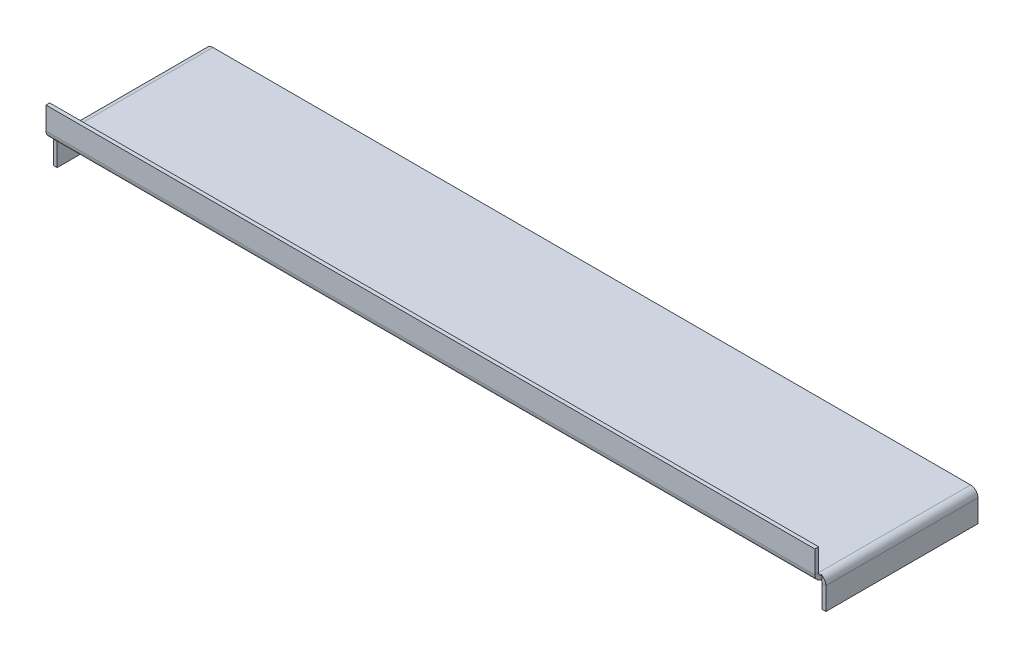
SolidWorks part; units mm, degrees
note: The reader was unsure of these and kept them because the rebuilt part matched: flange length of "Edge-Flange1", "Edge-Flange2", "Edge-Flange3".
ref_plane "Front Plane" through (0, 0, 0) normal (0, 0, 1) x (1, 0, 0)
ref_plane "Top Plane" through (0, 0, 0) normal (0, 1, 0) x (1, 0, 0)
ref_plane "Right Plane" through (0, 0, 0) normal (1, 0, 0) x (0, 0, -1)
sketch "Sketch1" plane through (0, 0, 0) normal (0, 1, 0) x (1, 0, 0)
  line L1 (244.844, -50.8) -> (-244.844, -50.8)
  line L2 (244.844, -50.8) -> (244.844, 50.8)
  line L3 (244.844, 50.8) -> (-244.844, 50.8)
  line L4 (-244.844, -50.8) -> (-244.844, 50.8)
  line L5 (244.844, -50.8) -> (-244.844, 50.8) construction
  line L6 (244.844, 50.8) -> (-244.844, -50.8) construction
  point P0 (0, 0)
  dimension "D1" = 489.688
  dimension "D2" = 101.6
base flange "Base-Flange1" sketch "Sketch1" thickness 2.3622 reverse thickness direction no parameters "D1"=10
edge flange "Edge-Flange1" sketch "Sketch8" flange angle 90 flange length 19.05 flange position material inside bend radius 2.36 thickness 2.3622 relief rectangular parameters "D6"=10
sketch "Sketch8" plane through (0, 0, 50.8) normal (0, 0, 1) x (1, 0, 0)
  line L2 (-244.844, 0) -> (-244.844, 16.6878)
  line L3 (-244.844, 16.6878) -> (244.844, 16.6878)
  line L4 (244.844, 16.6878) -> (244.844, 0)
  line L11 (-244.844, 0) -> (244.844, 0) construction
  line L12 (-244.844, 0) -> (244.844, 0)
bend "EdgeBend1" bend radius 2.36 bend angle 90 parameters "D5"=1
edge flange "Edge-Flange2" sketch "Sketch11" flange angle 90 flange length 19.05 flange position material inside bend radius 2.36 thickness 2.3622 relief none parameters "D6"=10
sketch "Sketch11" plane through (-244.844, -2.3622, 0) normal (-1, 0, 0) x (0, 0, -1)
  line L0 (50.8, 0) -> (-46.0778, 0) construction
  line L1 (50.8, 0) -> (-46.0778, 0)
  line L2 (-46.0778, 0) -> (-46.0778, 16.6878)
  line L3 (-46.0778, 16.6878) -> (50.8, 16.6878)
  line L4 (50.8, 16.6878) -> (50.8, 0)
bend "EdgeBend2" bend radius 2.36 bend angle 90 parameters "D5"=2
edge flange "Edge-Flange3" sketch "Sketch14" flange angle 90 flange length 19.05 flange position material outside bend radius 2.36 thickness 2.3622 relief none parameters "D6"=10
sketch "Sketch14" plane through (244.844, -2.3622, 0) normal (1, 0, 0) x (0, 0, 1)
  line L2 (-50.8, 0) -> (-50.8, 16.6878)
  line L3 (-50.8, 16.6878) -> (46.0778, 16.6878)
  line L4 (46.0778, 16.6878) -> (46.0778, 0)
  line L7 (46.0778, 0) -> (-50.8, 0) construction
  line L8 (46.0778, 0) -> (-50.8, 0)
bend "EdgeBend3" bend radius 2.36 bend angle 90 parameters "D5"=3
sketch "Bend-Lines1" [suppressed] plane through (0, 0, 0) normal (0, 1, 0) x (1, 0, 0)
sketch "Bounding-Box1" [suppressed] plane through (0, 0, 0) normal (0, 1, 0) x (1, 0, 0)
sheet metal parameters "Sheet-Metal1" thickness 2.3622 parameters "D1"=10
flat pattern "Flat-Pattern1" [suppressed]
sketch "Bend-Lines2" plane through (0, 0, 0) normal (0, 1, 0) x (1, 0, 0)
sketch3d "Bounding-Box2" [suppressed]
  line L0 (-255.27, -88.9, 0) -> (255.27, -88.9, 0) construction
  line L1 (-255.27, 88.9, 0) -> (255.27, 88.9, 0) construction
  line L2 (-255.27, -88.9, 0) -> (-255.27, 88.9, 0) construction
  line L3 (255.27, -88.9, 0) -> (255.27, 88.9, 0) construction
sheet metal parameters "Sheet-Metal2" thickness 2.3622 parameters "D1"=10
flat pattern "Flat-Pattern1"
sketch "Bend-Lines2" plane through (0, 0, 0) normal (0, 1, 0) x (1, 0, 0)
  line L0 (-255.27, -86.959) -> (255.27, -86.959) construction
  line L1 (-255.27, -86.959) -> (255.27, -86.959) construction
sketch3d "Bounding-Box2" [suppressed]
  line L0 (255.27, -104.0679, 0) -> (-255.27, -104.0679, 0) construction
  line L1 (255.27, 88.9, 0) -> (-255.27, 88.9, 0) construction
  line L2 (255.27, -104.0679, 0) -> (255.27, 88.9, 0) construction
  line L3 (-255.27, -104.0679, 0) -> (-255.27, 88.9, 0) construction
bend of the flat pattern "Flatten-<EdgeBend1>1"
sheet metal parameters "Sheet-Metal3" thickness 2.3622 parameters "D1"=10
flat pattern "Flat-Pattern1"
sketch "Bend-Lines2" plane through (0, 0, 0) normal (0, 1, 0) x (1, 0, 0)
  line L0 (-255.27, -86.959) -> (255.27, -86.959) construction
  line L1 (-255.27, -86.959) -> (255.27, -86.959) construction
  line L2 (-253.329, 88.9) -> (-253.329, -84.1778) construction
  line L3 (-253.329, 88.9) -> (-253.329, -84.1778) construction
sketch3d "Bounding-Box2" [suppressed]
  line L0 (255.27, -104.0679, 0) -> (-270.4379, -104.0679, 0) construction
  line L1 (255.27, 88.9, 0) -> (-270.4379, 88.9, 0) construction
  line L2 (255.27, -104.0679, 0) -> (255.27, 88.9, 0) construction
  line L3 (-270.4379, -104.0679, 0) -> (-270.4379, 88.9, 0) construction
bend of the flat pattern "Flatten-<EdgeBend1>1"
bend of the flat pattern "Flatten-<EdgeBend2>1"
sheet metal parameters "Sheet-Metal4" thickness 2.3622 parameters "D1"=10
flat pattern "Flat-Pattern1"
sketch "Bend-Lines2" plane through (0, 0, 0) normal (0, 1, 0) x (1, 0, 0)
  line L0 (-244.844, -48.859) -> (244.844, -48.859) construction
  line L1 (-244.844, -48.859) -> (244.844, -48.859) construction
  line L2 (-242.903, 50.8) -> (-242.903, -46.0778) construction
  line L3 (-242.903, 50.8) -> (-242.903, -46.0778) construction
  line L4 (245.2652, -46.0778) -> (245.2652, 50.8) construction
  line L5 (245.2652, -46.0778) -> (245.2652, 50.8) construction
sketch3d "Bounding-Box2" [suppressed]
  line L0 (262.3741, -65.9679, 0) -> (-260.0119, -65.9679, 0) construction
  line L1 (262.3741, 50.8, 0) -> (-260.0119, 50.8, 0) construction
  line L2 (262.3741, -65.9679, 0) -> (262.3741, 50.8, 0) construction
  line L3 (-260.0119, -65.9679, 0) -> (-260.0119, 50.8, 0) construction
bend of the flat pattern "Flatten-<EdgeBend1>1"
bend of the flat pattern "Flatten-<EdgeBend2>1"
bend of the flat pattern "Flatten-<EdgeBend3>1"
